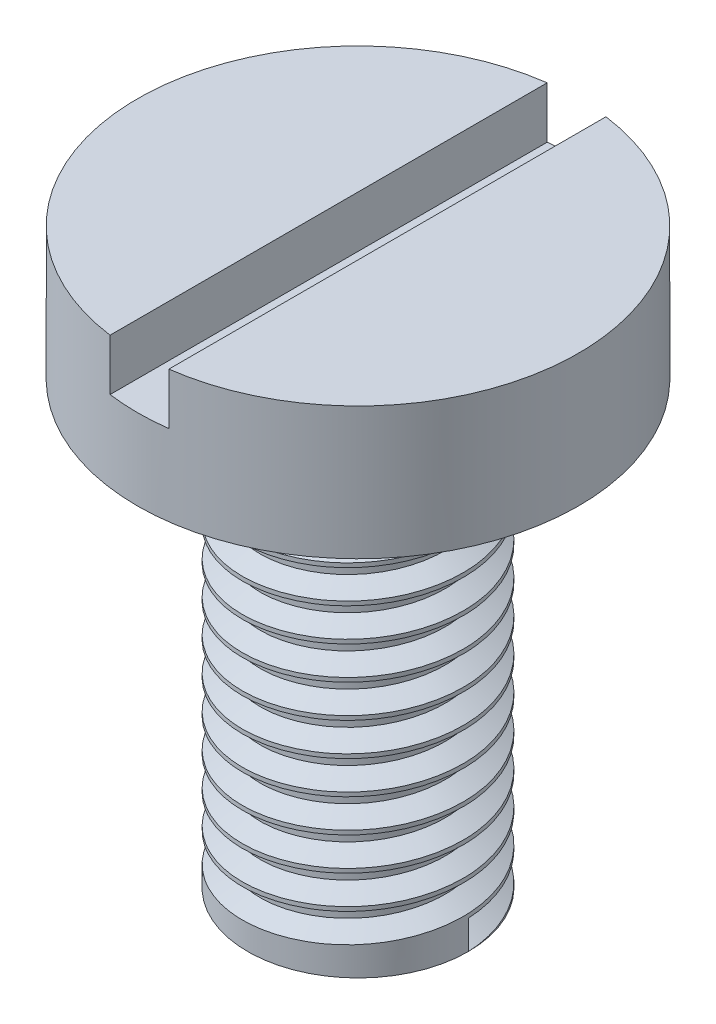
SolidWorks part; units mm, degrees
material "Brass"
ref_plane "Front Plane" through (0, 0, 0) normal (0, 0, 1) x (1, 0, 0)
ref_plane "Top Plane" through (0, 0, 0) normal (0, 1, 0) x (1, 0, 0)
ref_plane "Right Plane" through (0, 0, 0) normal (1, 0, 0) x (0, 0, -1)
sketch "Sketch1" plane through (0, 0, 0) normal (0, 1, 0) x (1, 0, 0)
  circle A0 centre (0, 0) radius 3
  dimension "D1" = 6
extrude "Boss-Extrude1" add sketch "Sketch1" along normal blind 1.8
sketch "Sketch2" plane through (0, 0, 0) normal (0, -1, 0) x (1, 0, 0)
  circle A0 centre (0, 0) radius 1.5
  dimension "D1" = 3
extrude "Boss-Extrude2" add sketch "Sketch2" along normal blind 6
thread "Thread1" pitch 0.45 method cut profile "Thread Profile1" start angle 0, offset 0, length 0, pitch 0.45, diameter 3
ref_plane "Plane1" through (1.5, -6, 0) normal (0, 0, 1) x (1, 0, 0)
sketch "Thread Profile1" plane through (1.5, -6, 0) normal (0, 0, 1) x (1, 0, 0)
  line L0 (0, 0) -> (0, 0.45) construction
  line L11 (0, 0) -> (0, 0.3937)
  line L12 (0, 0.3937) -> (-0.2436, 0.2531)
  line L13 (-0.2436, 0.2531) -> (-0.2436, 0.1406)
  line L15 (-0.2436, 0.1406) -> (0, 0)
  line L17 (-0.2436, 0.1969) -> (0, 0.1969) construction
  point P2 (0, 0)
  dimension "Pitch" = 0.45
  dimension "Profile_Angle" = 60
  dimension "Profile_Land" = 0.1125
  dimension "Profile_Height" = 0.2436
sketch "Sketch6" plane through (0, 1.8, 0) normal (0, 1, 0) x (1, 0, 0)
  line L0 (0, -1000) -> (0, 49000) construction
  line L2 (0.4, -3.5) -> (-0.4, -3.5)
  line L3 (0.4, -3.5) -> (0.4, 3.5)
  line L4 (0.4, 3.5) -> (-0.4, 3.5)
  line L5 (-0.4, -3.5) -> (-0.4, 3.5)
  line L6 (0.4, -3.5) -> (-0.4, 3.5) construction
  line L7 (0.4, 3.5) -> (-0.4, -3.5) construction
  point P1 (0, 0)
  dimension "D1" = 0.8
  dimension "D2" = 7
extrude "Cut-Extrude1" cut sketch "Sketch6" against normal blind 0.7
